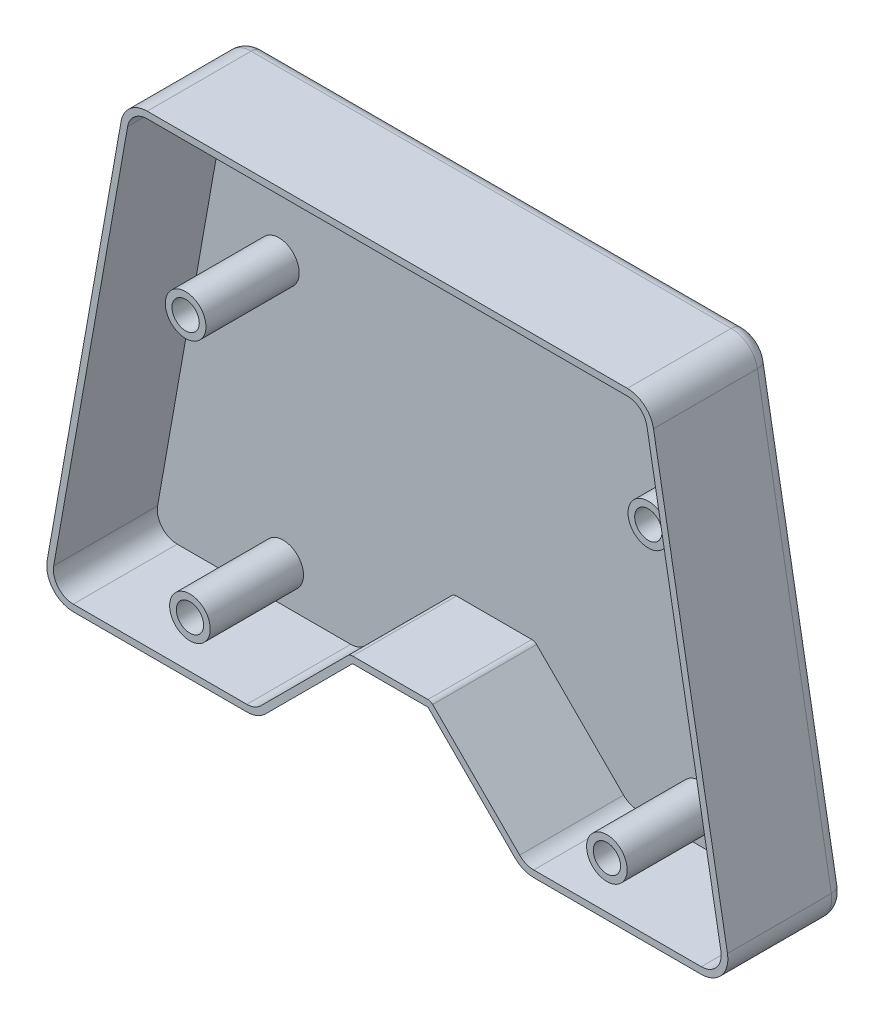
SolidWorks part; units mm, degrees
ref_plane "前视基准面" through (0, 0, 0) normal (0, 0, 1) x (1, 0, 0)
ref_plane "上视基准面" through (0, 0, 0) normal (0, 1, 0) x (1, 0, 0)
ref_plane "右视基准面" through (0, 0, 0) normal (1, 0, 0) x (0, 0, -1)
other "Configuration Table"
sketch "草图1" plane through (0, 0, 0) normal (0, 0, 1) x (1, 0, 0)
  line L94 (-18.737, -43.8075) -> (7.3198, -43.8075)
  line L95 (10.1392, -42.6396) -> (23.1917, -29.5872)
  line L96 (23.2007, -29.5835) -> (34.5123, -29.5835)
  line L97 (34.5213, -29.5872) -> (47.5737, -42.6396)
  line L98 (50.3932, -43.8075) -> (75.5524, -43.8075)
  line L99 (79.4785, -39.1247) -> (68.3761, 23.5504)
  line L100 (64.4499, 26.8422) -> (-7.6345, 26.8422)
  line L101 (-11.5607, 23.5504) -> (-22.6632, -39.1247)
  line L102 (-18.737, -43.8075) -> (7.3198, -43.8075)
  line L103 (10.1392, -42.6396) -> (23.1917, -29.5872)
  line L104 (23.2007, -29.5835) -> (34.5123, -29.5835)
  line L105 (34.5213, -29.5872) -> (47.5737, -42.6396)
  line L106 (50.3932, -43.8075) -> (75.5524, -43.8075)
  line L107 (79.4785, -39.1247) -> (68.3761, 23.5504)
  line L108 (64.4499, 26.8422) -> (-7.6345, 26.8422)
  line L109 (-11.5607, 23.5504) -> (-22.6632, -39.1247)
  arc A67 (-7.6345, 26.8422) -> (-11.5607, 23.5504) centre (-7.6345, 22.8549) ccw
  arc A68 (-22.6632, -39.1247) -> (-18.737, -43.8075) centre (-18.737, -39.8202) ccw
  arc A69 (7.3198, -43.8075) -> (10.1392, -42.6396) centre (7.3198, -39.8202) ccw
  arc A70 (23.2007, -29.5835) -> (23.1917, -29.5872) centre (23.2007, -29.5962) ccw
  arc A71 (34.5213, -29.5872) -> (34.5123, -29.5835) centre (34.5123, -29.5962) ccw
  arc A72 (47.5737, -42.6396) -> (50.3932, -43.8075) centre (50.3932, -39.8202) ccw
  arc A73 (75.5524, -43.8075) -> (79.4785, -39.1247) centre (75.5524, -39.8202) ccw
  arc A74 (68.3761, 23.5504) -> (64.4499, 26.8422) centre (64.4499, 22.8549) ccw
  arc A75 (-7.6345, 26.8422) -> (-11.5607, 23.5504) centre (-7.6345, 22.8549) ccw
  arc A76 (-22.6632, -39.1247) -> (-18.737, -43.8075) centre (-18.737, -39.8202) ccw
  arc A77 (7.3198, -43.8075) -> (10.1392, -42.6396) centre (7.3198, -39.8202) ccw
  arc A78 (23.2007, -29.5835) -> (23.1917, -29.5872) centre (23.2007, -29.5962) ccw
  arc A79 (34.5213, -29.5872) -> (34.5123, -29.5835) centre (34.5123, -29.5962) ccw
  arc A80 (47.5737, -42.6396) -> (50.3932, -43.8075) centre (50.3932, -39.8202) ccw
  arc A81 (75.5524, -43.8075) -> (79.4785, -39.1247) centre (75.5524, -39.8202) ccw
  arc A82 (68.3761, 23.5504) -> (64.4499, 26.8422) centre (64.4499, 22.8549) ccw
  point P0 (0, 0)
  dimension "D1" = 2
extrude "凸台-拉伸1" add sketch "草图1" along normal blind 2
sketch "草图4" plane through (0, 0, 2) normal (0, 0, 1) x (1, 0, 0)
  arc A9 (63.9498, 9.1069) -> (68.0498, 9.1069) centre (65.9998, 9.1069) ccw
  arc A10 (68.0498, 9.1069) -> (63.9498, 9.1069) centre (65.9998, 9.1069) ccw
  arc A11 (63.9498, 9.1069) -> (68.0498, 9.1069) centre (65.9998, 9.1069) ccw
  arc A12 (68.0498, 9.1069) -> (63.9498, 9.1069) centre (65.9998, 9.1069) ccw
  arc A22 (-0.7724, -37.3752) -> (-4.8724, -37.3752) centre (-2.8224, -37.3752) ccw
  arc A23 (-4.8724, -37.3752) -> (-0.7724, -37.3752) centre (-2.8224, -37.3752) ccw
  arc A24 (-0.7724, -37.3752) -> (-4.8724, -37.3752) centre (-2.8224, -37.3752) ccw
  arc A25 (-4.8724, -37.3752) -> (-0.7724, -37.3752) centre (-2.8224, -37.3752) ccw
  arc A29 (61.8277, -37.3752) -> (57.7277, -37.3752) centre (59.7777, -37.3752) ccw
  arc A30 (57.7277, -37.3752) -> (61.8277, -37.3752) centre (59.7777, -37.3752) ccw
  arc A31 (61.8277, -37.3752) -> (57.7277, -37.3752) centre (59.7777, -37.3752) ccw
  arc A32 (57.7277, -37.3752) -> (61.8277, -37.3752) centre (59.7777, -37.3752) ccw
  arc A34 (-5.8724, -37.3752) -> (0.2276, -37.3752) centre (-2.8224, -37.3752) ccw
  arc A35 (0.2276, -37.3752) -> (-5.8724, -37.3752) centre (-2.8224, -37.3752) ccw
  arc A36 (-1.4194, 1.6139) -> (-5.5194, 1.6139) centre (-3.4694, 1.6139) ccw
  arc A37 (-5.5194, 1.6139) -> (-1.4194, 1.6139) centre (-3.4694, 1.6139) ccw
  arc A38 (-1.4194, 1.6139) -> (-5.5194, 1.6139) centre (-3.4694, 1.6139) ccw
  arc A39 (-5.5194, 1.6139) -> (-1.4194, 1.6139) centre (-3.4694, 1.6139) ccw
  arc A40 (56.7277, -37.3752) -> (62.8277, -37.3752) centre (59.7777, -37.3752) ccw
  arc A41 (62.8277, -37.3752) -> (56.7277, -37.3752) centre (59.7777, -37.3752) ccw
  arc A42 (69.0498, 9.1069) -> (62.9498, 9.1069) centre (65.9998, 9.1069) ccw
  arc A43 (62.9498, 9.1069) -> (69.0498, 9.1069) centre (65.9998, 9.1069) ccw
  arc A44 (-6.5194, 1.6139) -> (-0.4194, 1.6139) centre (-3.4694, 1.6139) ccw
  arc A45 (-0.4194, 1.6139) -> (-6.5194, 1.6139) centre (-3.4694, 1.6139) ccw
  dimension "D1" = 0.4
  dimension "D2" = 0.4
  dimension "D3" = 0.4
  dimension "D4" = 0.4
  dimension "D5" = 1
extrude "凸台-拉伸2" add sketch "草图4" along normal blind 14
sketch "草图6" plane through (0, 0, 2) normal (0, 0, 1) x (1, 0, 0)
  line L0 (-10.576, 23.376) -> (-21.6785, -39.2991)
  line L1 (-18.737, -42.8075) -> (7.3198, -42.8075)
  line L2 (9.4321, -41.9325) -> (22.4845, -28.8801)
  line L3 (23.2007, -28.5835) -> (34.5123, -28.5835)
  line L4 (35.2284, -28.8801) -> (48.2808, -41.9325)
  line L5 (50.3932, -42.8075) -> (75.5524, -42.8075)
  line L6 (78.4939, -39.2991) -> (67.3914, 23.376)
  line L7 (64.4499, 25.8422) -> (-7.6345, 25.8422)
  line L8 (-11.5607, 23.5504) -> (-22.6632, -39.1247)
  line L9 (-18.737, -43.8075) -> (7.3198, -43.8075)
  line L10 (10.1392, -42.6396) -> (23.1917, -29.5872)
  line L11 (23.2007, -29.5835) -> (34.5123, -29.5835)
  line L12 (34.5213, -29.5872) -> (47.5737, -42.6396)
  line L13 (50.3932, -43.8075) -> (75.5524, -43.8075)
  line L14 (79.4785, -39.1247) -> (68.3761, 23.5504)
  line L15 (64.4499, 26.8422) -> (-7.6345, 26.8422)
  line L16 (-11.5607, 23.5504) -> (-22.6632, -39.1247)
  line L17 (-18.737, -43.8075) -> (7.3198, -43.8075)
  line L18 (10.1392, -42.6396) -> (23.1917, -29.5872)
  line L19 (23.2007, -29.5835) -> (34.5123, -29.5835)
  line L20 (34.5213, -29.5872) -> (47.5737, -42.6396)
  line L21 (50.3932, -43.8075) -> (75.5524, -43.8075)
  line L22 (79.4785, -39.1247) -> (68.3761, 23.5504)
  line L23 (64.4499, 26.8422) -> (-7.6345, 26.8422)
  arc A0 (-21.6785, -39.2991) -> (-18.737, -42.8075) centre (-18.737, -39.8202) ccw
  arc A1 (7.3198, -42.8075) -> (9.4321, -41.9325) centre (7.3198, -39.8202) ccw
  arc A2 (23.2007, -28.5835) -> (22.4845, -28.8801) centre (23.2007, -29.5962) ccw
  arc A3 (35.2284, -28.8801) -> (34.5123, -28.5835) centre (34.5123, -29.5962) ccw
  arc A4 (48.2808, -41.9325) -> (50.3932, -42.8075) centre (50.3932, -39.8202) ccw
  arc A5 (75.5524, -42.8075) -> (78.4939, -39.2991) centre (75.5524, -39.8202) ccw
  arc A6 (67.3914, 23.376) -> (64.4499, 25.8422) centre (64.4499, 22.8549) ccw
  arc A7 (-7.6345, 25.8422) -> (-10.576, 23.376) centre (-7.6345, 22.8549) ccw
  arc A8 (-7.6345, 26.8422) -> (-11.5607, 23.5504) centre (-7.6345, 22.8549) ccw
  arc A9 (-22.6632, -39.1247) -> (-18.737, -43.8075) centre (-18.737, -39.8202) ccw
  arc A10 (7.3198, -43.8075) -> (10.1392, -42.6396) centre (7.3198, -39.8202) ccw
  arc A11 (23.2007, -29.5835) -> (23.1917, -29.5872) centre (23.2007, -29.5962) ccw
  arc A12 (34.5213, -29.5872) -> (34.5123, -29.5835) centre (34.5123, -29.5962) ccw
  arc A13 (47.5737, -42.6396) -> (50.3932, -43.8075) centre (50.3932, -39.8202) ccw
  arc A14 (75.5524, -43.8075) -> (79.4785, -39.1247) centre (75.5524, -39.8202) ccw
  arc A15 (68.3761, 23.5504) -> (64.4499, 26.8422) centre (64.4499, 22.8549) ccw
  arc A16 (-7.6345, 26.8422) -> (-11.5607, 23.5504) centre (-7.6345, 22.8549) ccw
  arc A17 (-22.6632, -39.1247) -> (-18.737, -43.8075) centre (-18.737, -39.8202) ccw
  arc A18 (7.3198, -43.8075) -> (10.1392, -42.6396) centre (7.3198, -39.8202) ccw
  arc A19 (23.2007, -29.5835) -> (23.1917, -29.5872) centre (23.2007, -29.5962) ccw
  arc A20 (34.5213, -29.5872) -> (34.5123, -29.5835) centre (34.5123, -29.5962) ccw
  arc A21 (47.5737, -42.6396) -> (50.3932, -43.8075) centre (50.3932, -39.8202) ccw
  arc A22 (75.5524, -43.8075) -> (79.4785, -39.1247) centre (75.5524, -39.8202) ccw
  arc A23 (68.3761, 23.5504) -> (64.4499, 26.8422) centre (64.4499, 22.8549) ccw
  dimension "D1" = 0
  dimension "D2" = 1
extrude "凸台-拉伸3" add sketch "草图6" along normal up to surface (15.6001 mm away)
sketch "草图11" plane through (96.4894, -33.9679, 32.6745) normal (1, 0, 0) x (0, 0, -1)
  line L0 (32.6745, -9.8396) -> (23.8745, -9.8396)
  line L1 (15.0745, -9.8396) -> (32.6745, -9.8396) construction
  line L2 (23.8745, -9.8396) -> (32.6745, 29.1804)
  line L3 (32.6745, -5.1568) -> (32.6745, 57.5183) construction
  line L4 (32.6745, 29.1804) -> (32.6745, -9.8396)
  dimension "D1" = 40
fillet "圆角1" radius 2 16 edges at (78.6078, -42.382, 0) (62.9728, -43.8075, 0) (48.8673, -43.504, 0) (41.0475, -36.1134, 0) (34.5171, -29.5844, 0) (28.8565, -29.5835, 0) (23.1958, -29.5844, 0) (16.6655, -36.1134, 0) (8.8457, -43.504, 0) (-5.7086, -43.8075, 0) (-21.7925, -42.382, 0) (-17.1119, -7.7871, 0) (-10.1963, 25.9104, 0) (28.4077, 26.8422, 0) (67.0117, 25.9104, 0) (73.9273, -7.7871, 0)
